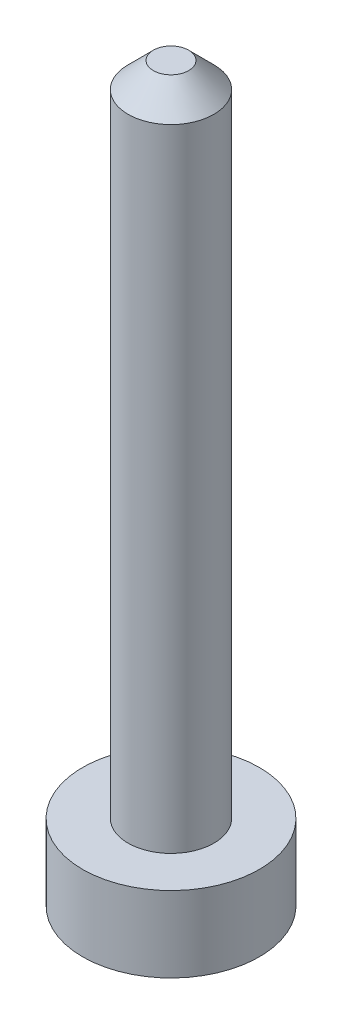
SolidWorks part; units mm, degrees
ref_plane "Спереди" through (0, 0, 0) normal (0, 0, 1) x (1, 0, 0)
ref_plane "Сверху" through (0, 0, 0) normal (0, 1, 0) x (1, 0, 0)
ref_plane "Справа" through (0, 0, 0) normal (1, 0, 0) x (0, 0, -1)
sketch "Эскиз1" plane through (0, 0, 0) normal (0, 1, 0) x (1, 0, 0)
  circle A0 centre (0, 0) radius 3.5
  circle A1 centre (0, 0) radius 1.7
  dimension "D1" = 7
  dimension "D2" = 3.4
extrude "Бобышка-Вытянуть1" add sketch "Эскиз1" against normal blind 3 contours A1 | A0 A1 region at (-3.401, 0, 0) region at (0, 0, 0)
extrude "Бобышка-Вытянуть2" add sketch "Эскиз1<3>" along normal blind 26 contours A1 region at (0, 0, 0)
sketch "Эскиз1<3>" plane through (0, 0, 0) normal (0, 1, 0) x (1, 0, 0) same geometry as "Эскиз1"
chamfer "Фаска1" distance 1 angle 45 1 edges at (0, 26, 1.7)
